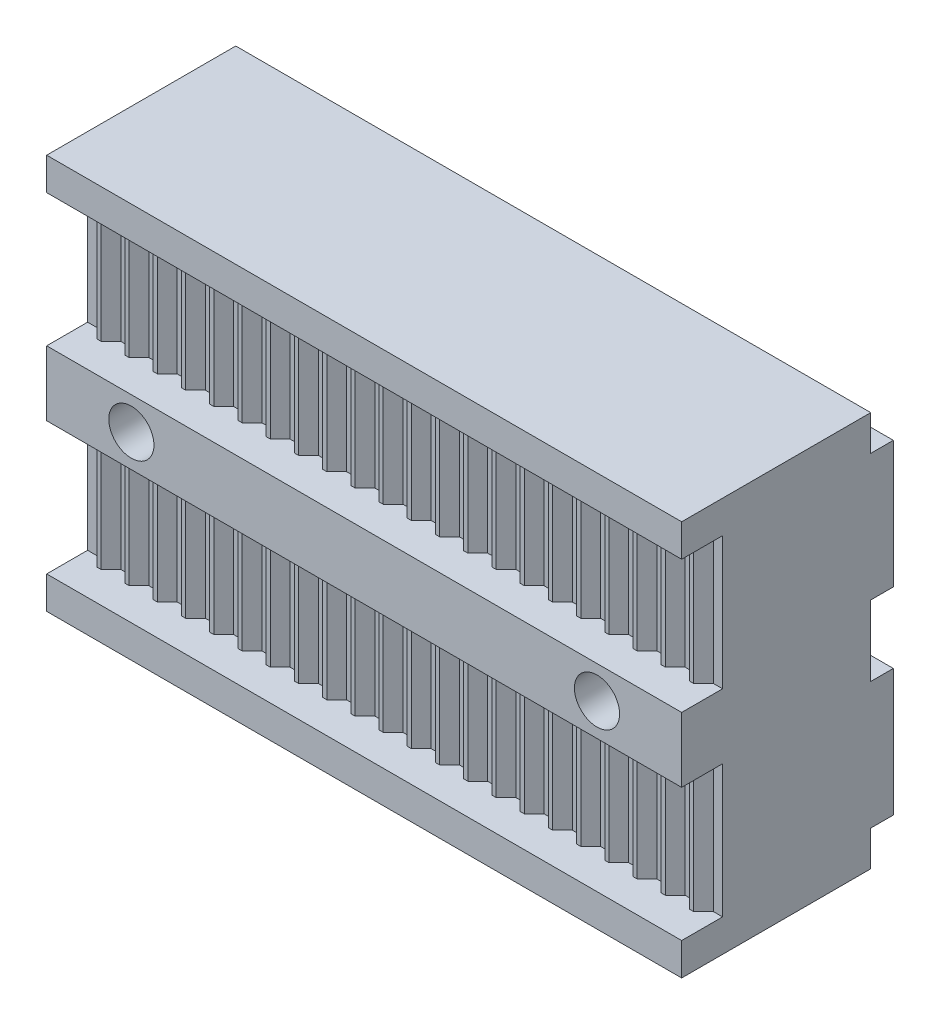
SolidWorks part; units mm, degrees
ref_plane "Спереди" through (0, 0, 0) normal (0, 0, 1) x (1, 0, 0)
ref_plane "Сверху" through (0, 0, 0) normal (0, 1, 0) x (1, 0, 0)
ref_plane "Справа" through (0, 0, 0) normal (1, 0, 0) x (0, 0, -1)
sketch "Эскиз1" plane through (0, 0, 0) normal (0, 0, 1) x (1, 0, 0)
  line L1 (0, -28) -> (-45, -28)
  line L2 (0, -28) -> (0, 0)
  line L3 (0, 0) -> (-45, 0)
  line L4 (-45, -28) -> (-45, 0)
  dimension "D1" = 28
  dimension "D2" = 45
extrude "Бобышка-Вытянуть1" add sketch "Эскиз1" along normal blind 13.4
sketch "Эскиз2" plane through (0, 0, 0) normal (0, 1, 0) x (1, 0, 0)
  line L6 (-45, 0) -> (-45, 1.6)
  line L90 (0, 0) -> (0, 1.6)
  line L91 (0, 0) -> (-45, 0)
  line L93 (-45, 1.6) -> (0, 1.6)
  dimension "D5" = 1.6
extrude "Бобышка-Вытянуть2" add sketch "Эскиз2" against normal blind 9 from offset 2.5 offset against normal yes
extrude "Бобышка-Вытянуть3" add sketch "Эскиз2<2>" against normal blind 9 from offset 16.5 offset against normal yes
sketch "Эскиз2<2>" plane through (0, 0, 0) normal (0, 1, 0) x (1, 0, 0) same geometry as "Эскиз2"
sketch "Эскиз3" plane through (0, 0, 13.4) normal (0, 0, 1) x (1, 0, 0)
  line L1 (-45, -2.3) -> (0, -2.3)
  line L2 (-45, -2.3) -> (-45, -11.7)
  line L3 (-45, -11.7) -> (0, -11.7)
  line L4 (0, -2.3) -> (0, -11.7)
  line L6 (-45, 0) -> (-45, -28) construction
  line L7 (0, -28) -> (0, 0) construction
  line L8 (0, 0) -> (-45, 0) construction
  line L9 (-45, -16.3) -> (0, -16.3)
  line L10 (-45, -16.3) -> (-45, -25.7)
  line L11 (-45, -25.7) -> (0, -25.7)
  line L12 (0, -16.3) -> (0, -25.7)
  line L13 (-45, -28) -> (0, -28) construction
  dimension "D1" = 9.4
  dimension "D2" = 45
  dimension "D3" = 9.4
  dimension "D4" = 45
  dimension "D5" = 4.6
  dimension "D6" = 2.3
  dimension "D7" = 2.3
extrude "Вырез-Вытянуть1" cut sketch "Эскиз3" against normal blind 2.9
sketch "Эскиз4" plane through (0, 0, 13.4) normal (0, 0, 1) x (1, 0, 0)
  line L0 (-45, -11.7) -> (-45, -16.3) construction
  line L1 (0, -16.3) -> (0, -11.7) construction
  circle A0 centre (-39, -14) radius 1.6
  circle A1 centre (-6, -14) radius 1.6
  point P9 (-45, -14)
  dimension "D1" = 3.2
  dimension "D2" = 3.2
  dimension "D4" = 6
  dimension "D3" = 6
extrude "Вырез-Вытянуть2" cut sketch "Эскиз4" against normal through all
sketch "Эскиз5" plane through (0, -2.3, 0) normal (0, -1, 0) x (1, 0, 0)
  line L0 (-45, 10.5) -> (-44.35, 10.5)
  line L1 (0, 10.5) -> (-45, 10.5) construction
  line L2 (-44.35, 10.5) -> (-43.65, 11.2)
  line L3 (-43.65, 11.2) -> (-43.35, 11.2)
  line L4 (-43.35, 11.2) -> (-42.65, 10.5)
  line L5 (-42.65, 10.5) -> (-42.35, 10.5)
  line L6 (-45, 10.5) -> (-45, 9.5)
  line L7 (-42.35, 10.5) -> (-41.65, 11.2)
  line L8 (-41.65, 11.2) -> (-41.35, 11.2)
  line L9 (-41.35, 11.2) -> (-40.65, 10.5)
  line L10 (-40.65, 10.5) -> (-40.35, 10.5)
  line L11 (-40.35, 10.5) -> (-39.65, 11.2)
  line L12 (-39.65, 11.2) -> (-39.35, 11.2)
  line L13 (-39.35, 11.2) -> (-38.65, 10.5)
  line L14 (-38.65, 10.5) -> (-38.35, 10.5)
  line L15 (-38.35, 10.5) -> (-37.65, 11.2)
  line L16 (-37.65, 11.2) -> (-37.35, 11.2)
  line L17 (-37.35, 11.2) -> (-36.65, 10.5)
  line L18 (-36.65, 10.5) -> (-36.35, 10.5)
  line L19 (-36.35, 10.5) -> (-35.65, 11.2)
  line L20 (-35.65, 11.2) -> (-35.35, 11.2)
  line L21 (-35.35, 11.2) -> (-34.65, 10.5)
  line L22 (-34.65, 10.5) -> (-34.35, 10.5)
  line L23 (-34.35, 10.5) -> (-33.65, 11.2)
  line L24 (-33.65, 11.2) -> (-33.35, 11.2)
  line L25 (-33.35, 11.2) -> (-32.65, 10.5)
  line L26 (-32.65, 10.5) -> (-32.35, 10.5)
  line L27 (-32.35, 10.5) -> (-31.65, 11.2)
  line L28 (-31.65, 11.2) -> (-31.35, 11.2)
  line L29 (-31.35, 11.2) -> (-30.65, 10.5)
  line L30 (-30.65, 10.5) -> (-30.35, 10.5)
  line L31 (-30.35, 10.5) -> (-29.65, 11.2)
  line L32 (-29.65, 11.2) -> (-29.35, 11.2)
  line L33 (-29.35, 11.2) -> (-28.65, 10.5)
  line L34 (-28.65, 10.5) -> (-28.35, 10.5)
  line L35 (-28.35, 10.5) -> (-27.65, 11.2)
  line L36 (-27.65, 11.2) -> (-27.35, 11.2)
  line L37 (-27.35, 11.2) -> (-26.65, 10.5)
  line L38 (-26.65, 10.5) -> (-26.35, 10.5)
  line L39 (-26.35, 10.5) -> (-25.65, 11.2)
  line L40 (-25.65, 11.2) -> (-25.35, 11.2)
  line L41 (-25.35, 11.2) -> (-24.65, 10.5)
  line L42 (-24.65, 10.5) -> (-24.35, 10.5)
  line L43 (-24.35, 10.5) -> (-23.65, 11.2)
  line L44 (-23.65, 11.2) -> (-23.35, 11.2)
  line L45 (-23.35, 11.2) -> (-22.65, 10.5)
  line L46 (-22.65, 10.5) -> (-22.35, 10.5)
  line L47 (-22.35, 10.5) -> (-21.65, 11.2)
  line L48 (-21.65, 11.2) -> (-21.35, 11.2)
  line L49 (-21.35, 11.2) -> (-20.65, 10.5)
  line L50 (-20.65, 10.5) -> (-20.35, 10.5)
  line L51 (-20.35, 10.5) -> (-19.65, 11.2)
  line L52 (-19.65, 11.2) -> (-19.35, 11.2)
  line L53 (-19.35, 11.2) -> (-18.65, 10.5)
  line L54 (-18.65, 10.5) -> (-18.35, 10.5)
  line L55 (-18.35, 10.5) -> (-17.65, 11.2)
  line L56 (-17.65, 11.2) -> (-17.35, 11.2)
  line L57 (-17.35, 11.2) -> (-16.65, 10.5)
  line L58 (-16.65, 10.5) -> (-16.35, 10.5)
  line L59 (-16.35, 10.5) -> (-15.65, 11.2)
  line L60 (-15.65, 11.2) -> (-15.35, 11.2)
  line L61 (-15.35, 11.2) -> (-14.65, 10.5)
  line L62 (-14.65, 10.5) -> (-14.35, 10.5)
  line L63 (-14.35, 10.5) -> (-13.65, 11.2)
  line L64 (-13.65, 11.2) -> (-13.35, 11.2)
  line L65 (-13.35, 11.2) -> (-12.65, 10.5)
  line L66 (-12.65, 10.5) -> (-12.35, 10.5)
  line L67 (-12.35, 10.5) -> (-11.65, 11.2)
  line L68 (-11.65, 11.2) -> (-11.35, 11.2)
  line L69 (-11.35, 11.2) -> (-10.65, 10.5)
  line L70 (-10.65, 10.5) -> (-10.35, 10.5)
  line L71 (-10.35, 10.5) -> (-9.65, 11.2)
  line L72 (-9.65, 11.2) -> (-9.35, 11.2)
  line L73 (-9.35, 11.2) -> (-8.65, 10.5)
  line L74 (-8.65, 10.5) -> (-8.35, 10.5)
  line L75 (-8.35, 10.5) -> (-7.65, 11.2)
  line L76 (-7.65, 11.2) -> (-7.35, 11.2)
  line L77 (-7.35, 11.2) -> (-6.65, 10.5)
  line L78 (-6.65, 10.5) -> (-6.35, 10.5)
  line L79 (-6.35, 10.5) -> (-5.65, 11.2)
  line L80 (-5.65, 11.2) -> (-5.35, 11.2)
  line L81 (-5.35, 11.2) -> (-4.65, 10.5)
  line L82 (-4.65, 10.5) -> (-4.35, 10.5)
  line L83 (-4.35, 10.5) -> (-3.65, 11.2)
  line L84 (-3.65, 11.2) -> (-3.35, 11.2)
  line L85 (-3.35, 11.2) -> (-2.65, 10.5)
  line L86 (-2.65, 10.5) -> (-2.35, 10.5)
  line L87 (-2.35, 10.5) -> (-1.65, 11.2)
  line L88 (-1.65, 11.2) -> (-1.35, 11.2)
  line L89 (-1.35, 11.2) -> (-0.65, 10.5)
  line L90 (-0.65, 10.5) -> (0, 10.5)
  line L91 (-45, 9.5) -> (0, 9.5)
  line L92 (0, 10.5) -> (0, 9.5)
  line L93 (-0.65, 10.5) -> (-0.35, 10.5) [skipped]
  dimension "D1" = 45
  dimension "D2" = 45
  dimension "D3" = 0.7
  dimension "D4" = 2
  dimension "D5" = 0.65
  dimension "D6" = 1
  dimension "D7" = 22
extrude "Бобышка-Вытянуть4" add sketch "Эскиз5" along normal up to surface (9.4 mm away) up to face at (-22.5, -11.7, 11.95)
extrude "Бобышка-Вытянуть5" add sketch "Эскиз5<2>" along normal up to surface (23.4 mm away) from surface up to face at (-22.5, -25.7, 11.95) starting at face at (-22.5, -16.3, 11.95)
sketch "Эскиз5<2>" plane through (0, -2.3, 0) normal (0, -1, 0) x (1, 0, 0) same geometry as "Эскиз5"
